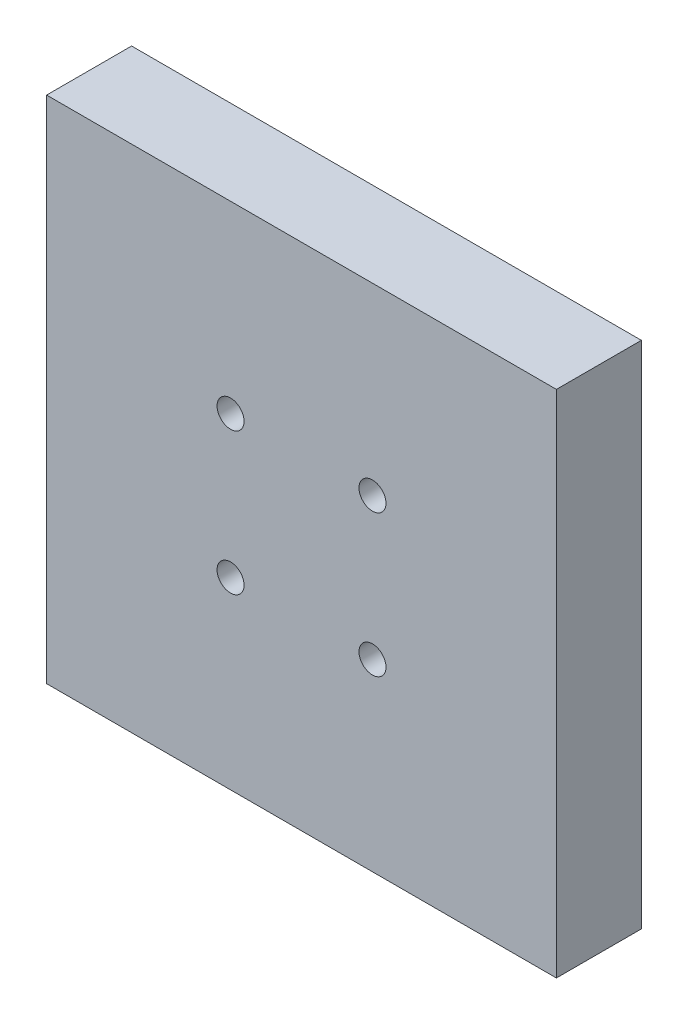
SolidWorks part; units mm, degrees
material "7050-T73510"
ref_plane "Front Plane" through (0, 0, 0) normal (0, 0, 1) x (1, 0, 0)
ref_plane "Top Plane" through (0, 0, 0) normal (0, 1, 0) x (1, 0, 0)
ref_plane "Right Plane" through (0, 0, 0) normal (1, 0, 0) x (0, 0, -1)
sketch "Sketch1" plane through (0, 0, 0) normal (0, 0, 1) x (1, 0, 0)
  line L0 (55, 0) -> (-55, 0) construction
  line L1 (-38.1, -38.1) -> (38.1, -38.1)
  line L2 (-38.1, -38.1) -> (-38.1, 38.1)
  line L3 (-38.1, 38.1) -> (38.1, 38.1)
  line L4 (38.1, -38.1) -> (38.1, 38.1)
  line L5 (-38.1, -38.1) -> (38.1, 38.1) construction
  line L6 (-38.1, 38.1) -> (38.1, -38.1) construction
  line L7 (-12.7, 38.1) -> (12.7, 38.1)
  line L8 (-12.7, 38.1) -> (-12.7, 44.45)
  line L9 (-12.7, 44.45) -> (12.7, 44.45)
  line L10 (12.7, 38.1) -> (12.7, 44.45)
  line L11 (-12.7, -44.45) -> (12.7, -44.45)
  line L12 (12.7, -38.1) -> (12.7, -44.45)
  line L13 (-12.7, -38.1) -> (12.7, -38.1)
  line L14 (-12.7, -38.1) -> (-12.7, -44.45)
  point P0 (0, 0)
  point P10 (0, 44.45)
  point P11 (0, 38.1)
  point P18 (0, -38.1)
  point P19 (0, -44.45)
  dimension "D1" = 76.2
  dimension "D2" = 76.2
  dimension "D3" = 25.4
  dimension "D4" = 6.35
extrude "Boss-Extrude1" add sketch "Sketch1" along normal blind 12.7 contours L1 L4 L3 L2 region at (0, 0, 0)
sketch "Sketch2" plane through (0, 0, 12.7) normal (0, 0, 1) x (1, 0, 0)
  line L0 (55, 0) -> (-55, 0) construction
  line L1 (-10.6066, -10.6066) -> (10.6066, -10.6066)
  line L2 (-10.6066, -10.6066) -> (-10.6066, 10.6066)
  line L3 (-10.6066, 10.6066) -> (10.6066, 10.6066)
  line L4 (10.6066, -10.6066) -> (10.6066, 10.6066)
  line L5 (-10.6066, -10.6066) -> (10.6066, 10.6066) construction
  line L6 (-10.6066, 10.6066) -> (10.6066, -10.6066) construction
  line L7 (0, -55) -> (0, 55) construction
  circle A0 centre (10.6066, 10.6066) radius 2.0193
  circle A1 centre (10.6066, -10.6066) radius 2.0193
  circle A2 centre (-10.6066, -10.6066) radius 2.0193
  circle A3 centre (-10.6066, 10.6066) radius 2.0193
  point P0 (0, 0)
  dimension "D2" = 4.0386
  dimension "D1" = 30
extrude "Cut-Extrude1" cut sketch "Sketch2" against normal through all contours A3 | A0 | A1 | A2
